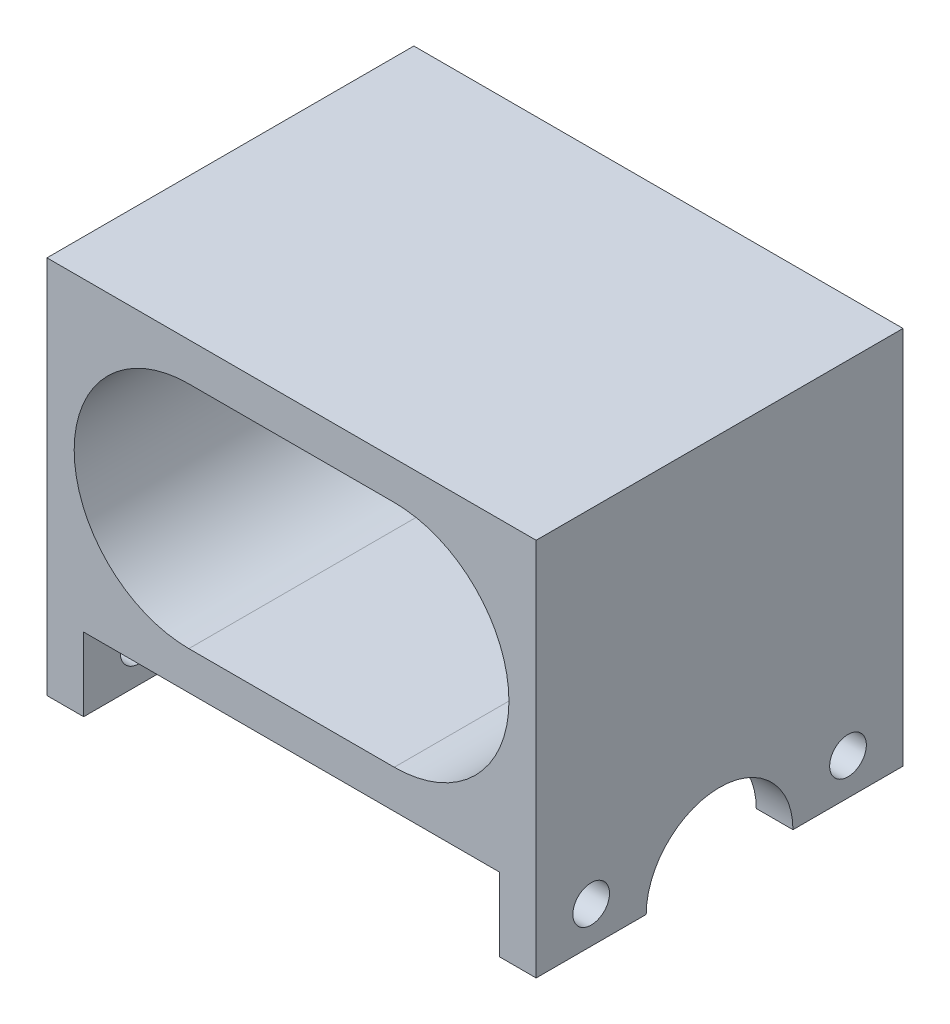
SolidWorks part; units mm, degrees
ref_plane "Front Plane" through (0, 0, 0) normal (0, 0, 1) x (1, 0, 0)
ref_plane "Top Plane" through (0, 0, 0) normal (0, 1, 0) x (1, 0, 0)
ref_plane "Right Plane" through (0, 0, 0) normal (1, 0, 0) x (0, 0, -1)
sketch "Sketch1" plane through (0, 0, 0) normal (0, 0, 1) x (1, 0, 0)
  line L0 (-8.4, 0) -> (8.4, 0) construction
  line L1 (-20, -12.5) -> (20, -12.5)
  line L2 (-20, -12.5) -> (-20, 12.5)
  line L3 (-20, 12.5) -> (20, 12.5)
  line L4 (20, -12.5) -> (20, 12.5)
  line L5 (-20, -12.5) -> (20, 12.5) construction
  line L6 (-20, 12.5) -> (20, -12.5) construction
  line L7 (-8.4, 9.375) -> (8.4, 9.375)
  line L8 (-8.4, -9.375) -> (8.4, -9.375)
  arc A0 (-8.4, 9.375) -> (-8.4, -9.375) centre (-8.4, 0) ccw
  arc A1 (8.4, -9.375) -> (8.4, 9.375) centre (8.4, 0) ccw
  point P0 (0, 0)
  point P8 (0, 0)
  dimension "D2" = 35.55
  dimension "D1" = 40
  dimension "D3" = 18.75
  dimension "D4" = 25
extrude "Boss-Extrude1" add sketch "Sketch1" along normal blind 15 and the other way blind 15
sketch "Sketch2" plane through (20, 0, 0) normal (1, 0, 0) x (0, 0, -1)
  line L0 (-15, -15.5) -> (-6, -15.5) construction
  line L1 (-15, -12.5) -> (-6, -12.5)
  line L2 (-15, -12.5) -> (-15, -18.5)
  line L3 (-15, -18.5) -> (-6, -18.5)
  line L4 (-6, -12.5) -> (-6, -18.5)
  line L5 (-15, -12.5) -> (15, -12.5) construction
  circle A0 centre (-10.5, -15.5) radius 1.5
  point P7 (-27.0027, -14.2307)
  point P8 (-26.6663, -15)
  point P12 (0, 0)
  point P14 (0, -12.5)
  dimension "D1" = 3
  dimension "D2" = 9
  dimension "D3" = 6
  dimension "D4" = 10.5
extrude "Boss-Extrude2" add sketch "Sketch2" against normal blind 3
mirror "Mirror1" about plane through (0, 0, 0) normal (0, 0, 1) of "Boss-Extrude2"
mirror "Mirror3" about plane through (0, 0, 0) normal (1, 0, 0) of "Mirror1"
fillet "Fillet1" radius 6 4 edges at (-18.5, -12.5, -6) (-18.5, -12.5, 6) (18.5, -12.5, -6) (18.5, -12.5, 6)
